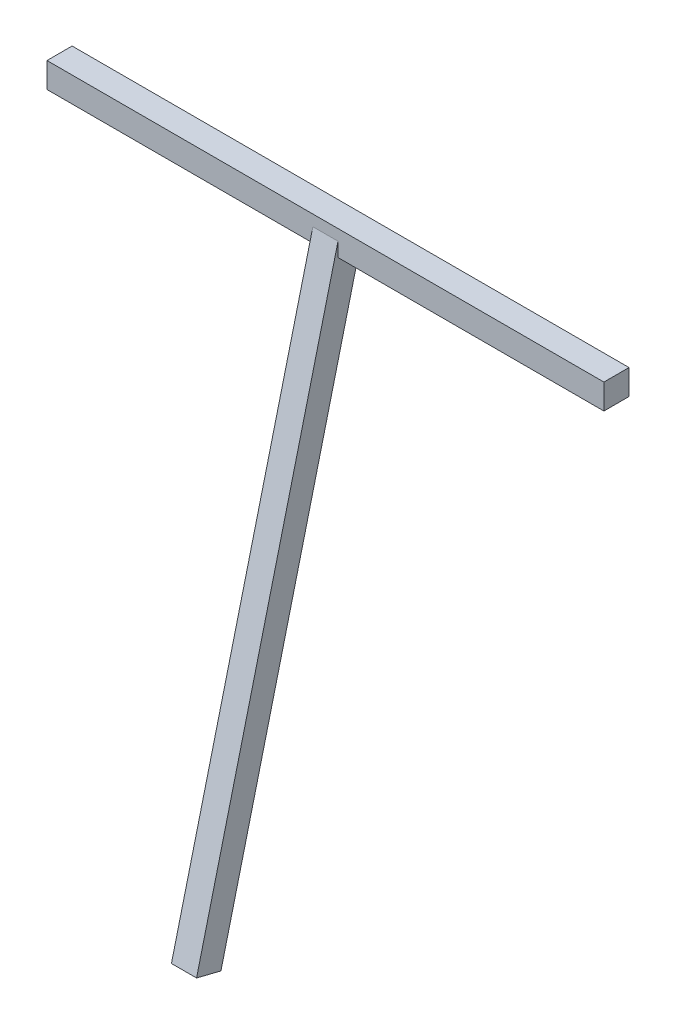
SolidWorks part; units mm, degrees
ref_plane "Front" through (0, 0, 0) normal (0, 0, 1) x (1, 0, 0)
ref_plane "Top" through (0, 0, 0) normal (0, 1, 0) x (1, 0, 0)
ref_plane "Right" through (0, 0, 0) normal (1, 0, 0) x (0, 0, -1)
sketch "Sketch1" plane through (0, 0, 0) normal (1, 0, 0) x (0, 0, -1)
  line L1 (15, 15) -> (-15, 15)
  line L2 (15, 15) -> (15, -15)
  line L3 (15, -15) -> (-15, -15)
  line L4 (-15, 15) -> (-15, -15)
  line L5 (15, 15) -> (-15, -15) construction
  line L6 (15, -15) -> (-15, 15) construction
  point P0 (0, 0)
  dimension "D1" = 30
  dimension "D2" = 30
extrude "Boss-Extrude1" add sketch "Sketch1" along normal blind 332.5 and the other way blind 332.5
sketch3d "3DSketch1" plane through (0, 0, 0) normal (0, 0, 1) x (1, 0, 0)
  dimension "D1" = 346
sketch "Sketch2" plane through (0, 0, 0) normal (0, -0.9703, 0.2419) x (-1, 0, 0)
  line L1 (15, -15) -> (-15, -15)
  line L2 (15, -15) -> (15, 15)
  line L3 (15, 15) -> (-15, 15)
  line L4 (-15, -15) -> (-15, 15)
  line L5 (15, -15) -> (-15, 15) construction
  line L6 (15, 15) -> (-15, -15) construction
  point P0 (0, 0)
  dimension "D1" = 30
  dimension "D2" = 30
extrude "Boss-Extrude2" add sketch "Sketch2" along normal blind 700
